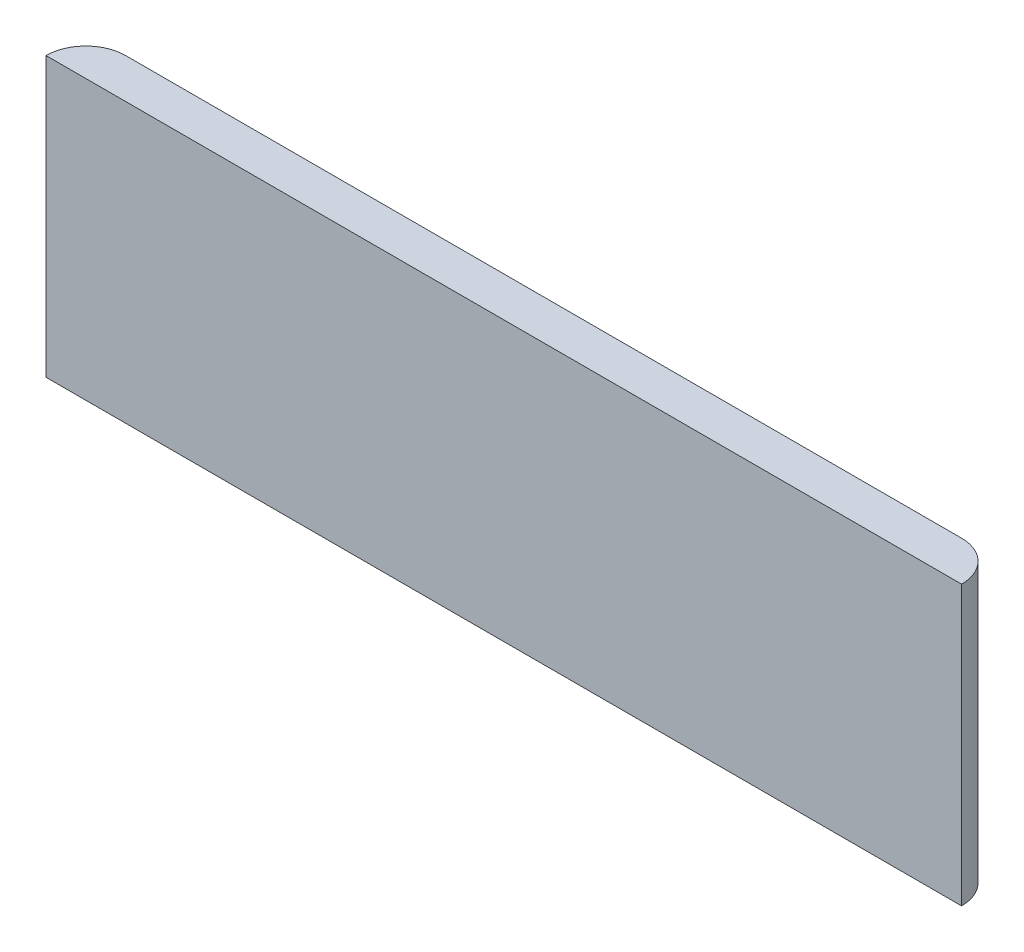
SolidWorks part; units mm, degrees
material "PE High Density"
ref_plane "Front Plane" through (0, 0, 0) normal (0, 0, 1) x (1, 0, 0)
ref_plane "Top Plane" through (0, 0, 0) normal (0, 1, 0) x (1, 0, 0)
ref_plane "Right Plane" through (0, 0, 0) normal (1, 0, 0) x (0, 0, -1)
sketch "Sketch1" plane through (0, 0, 0) normal (0, 1, 0) x (1, 0, 0)
  line L1 (0, 0) -> (-146.05, 0)
  line L2 (0, 0) -> (0, -6.35)
  line L3 (0, -6.35) -> (-146.05, -6.35)
  line L4 (-146.05, 0) -> (-146.05, -6.35)
  dimension "D1" = 146.05
  dimension "D2" = 6.35
extrude "Boss-Extrude1" add sketch "Sketch1" along normal blind 44.45
fillet "Fillet1" radius 6.35 6 edges at (-146.05, 44.45, 3.175) (0, 44.45, 3.175) (-146.05, 0, 3.175) (0, 0, 3.175) (-146.05, 22.225, 0) (0, 22.225, 0)
